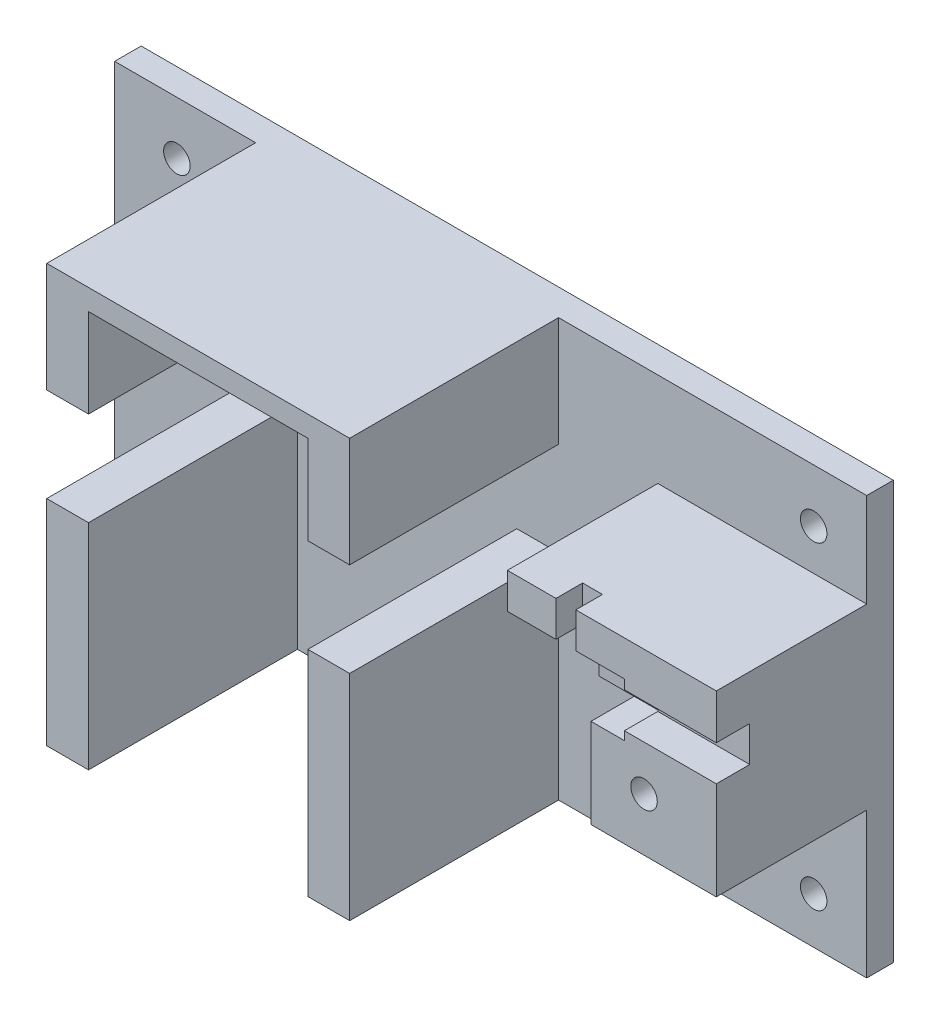
SolidWorks part; units mm, degrees
ref_plane "Front Plane" through (0, 0, 0) normal (0, 0, 1) x (1, 0, 0)
ref_plane "Top Plane" through (0, 0, 0) normal (0, 1, 0) x (1, 0, 0)
ref_plane "Right Plane" through (0, 0, 0) normal (1, 0, 0) x (0, 0, -1)
sketch "Sketch1" plane through (0, 0, 0) normal (0, 0, 1) x (1, 0, 0)
  line L1 (0, 0) -> (180, 0)
  line L2 (0, 0) -> (0, 100)
  line L3 (0, 100) -> (180, 100)
  line L4 (180, 0) -> (180, 100)
  dimension "D1" = 180
  dimension "D2" = 100
extrude "Boss-Extrude1" add sketch "Sketch1" along normal blind 6.35
sketch "Sketch2" plane through (0, 0, 6.35) normal (0, 0, 1) x (1, 0, 0)
  line L1 (96.25, 100) -> (106.25, 100)
  line L2 (96.25, 100) -> (96.25, 73.75)
  line L3 (96.25, 73.75) -> (106.25, 73.75)
  line L4 (106.25, 100) -> (106.25, 73.75)
  line L5 (180, 100) -> (0, 100) construction
  line L6 (0, 0) -> (180, 0) construction
  line L7 (70, 0) -> (70, 100)
  line L8 (96.25, 0) -> (106.25, 0)
  line L9 (96.25, 0) -> (96.25, 51.25)
  line L10 (96.25, 51.25) -> (106.25, 51.25)
  line L11 (106.25, 0) -> (106.25, 51.25)
  line L13 (96.25, 0) -> (96.25, 5)
  line L16 (0, 100) -> (0, 0) construction
  line L19 (70, 5) -> (70, 0)
  line L21 (96.25, 5) -> (96.25, 0)
  line L25 (43.75, 5) -> (43.75, 0)
  line L26 (43.75, 0) -> (43.75, 5)
  line L27 (33.75, 0) -> (33.75, 51.25)
  line L28 (43.75, 51.25) -> (33.75, 51.25)
  line L29 (43.75, 0) -> (43.75, 51.25)
  line L30 (43.75, 0) -> (33.75, 0)
  line L31 (33.75, 100) -> (33.75, 73.75)
  line L32 (43.75, 73.75) -> (33.75, 73.75)
  line L33 (43.75, 100) -> (43.75, 73.75)
  line L34 (43.75, 100) -> (33.75, 100)
  line L35 (43.75, 0) -> (43.75, 5)
  line L37 (43.75, 0) -> (96.25, 0)
  line L38 (43.75, 0) -> (43.75, 5)
  line L40 (96.25, 0) -> (96.25, 5)
  line L41 (43.75, 100) -> (96.25, 100)
  line L42 (43.75, 100) -> (43.75, 95)
  line L43 (43.75, 95) -> (96.25, 95)
  line L44 (96.25, 100) -> (96.25, 95)
  line M10 (0, 0) -> (180, 0)
  line M12 (180, 100) -> (0, 100)
  dimension "D1" = 10
  dimension "D2" = 10
  dimension "D3" = 26.25
  dimension "D4" = 70
  dimension "D5" = 22.5
  dimension "D6" = 26.25
  dimension "D8" = 5
extrude "Boss-Extrude3" add sketch "Sketch2" along normal blind 50 contours L33 L31 L32 M12 | L33 L43 L7 M12 | L7 L43 L2 M12 | L4 L2 L3 M12 | L25 L29 L28 L27 M10 | L11 L10 L9 M10 region at (101.25, 25.625, 6.35) region at (38.75, 25.625, 6.35) region at (101.25, 86.875, 6.35) region at (83.125, 97.5, 6.35) region at (56.875, 97.5, 6.35) region at (38.75, 86.875, 6.35)
sketch "Sketch3" plane through (0, 0, 6.35) normal (0, 0, 1) x (1, 0, 0)
  line L0 (180, 0) -> (180, 100) construction
  line L1 (180, 77.5) -> (150, 77.5)
  line L2 (180, 77.5) -> (180, 47.5)
  line L3 (180, 47.5) -> (150, 47.5)
  line L4 (150, 77.5) -> (150, 47.5)
  line L10 (180, 100) -> (106.25, 100) construction
  dimension "D1" = 30
  dimension "D2" = 30
  dimension "D3" = 22.5
extrude "Boss-Extrude4" add sketch "Sketch3" along normal blind 25.65
sketch "Sketch4" plane through (0, 0, 32) normal (0, 0, 1) x (1, 0, 0)
  line L0 (150, 77.5) -> (150, 47.5) construction
  line L1 (150, 69) -> (158, 69)
  line L2 (150, 69) -> (150, 56.2)
  line L3 (150, 56.2) -> (158, 56.2)
  line L4 (158, 69) -> (158, 56.2)
  line L5 (180, 77.5) -> (150, 77.5) construction
  line L6 (150, 69) -> (150, 77.5)
  line L7 (150, 77.5) -> (180, 77.5)
  line L8 (180, 77.5) -> (180, 47.5)
  line L9 (180, 47.5) -> (150, 47.5)
  line L10 (150, 47.5) -> (150, 56.2)
  line L12 (158, 58.25) -> (180, 58.25)
  line L13 (158, 58.25) -> (158, 66.75)
  line L14 (158, 66.75) -> (180, 66.75)
  line L15 (180, 58.25) -> (180, 66.75)
  line M8 (180, 47.5) -> (180, 77.5)
  line M9 (180, 77.5) -> (150, 77.5)
  line M10 (150, 77.5) -> (150, 47.5)
  line M11 (150, 47.5) -> (180, 47.5)
  dimension "D1" = 12.8
  dimension "D2" = 8.5
  dimension "D3" = 8
  dimension "D4" = 8.5
  dimension "D5" = 10.75
extrude "Boss-Extrude5" add sketch "Sketch4" along normal blind 10.35 contours L4 L14 L1 M8 M9 M10 | L12 L4 L3 M10 M11 M8 region at (165.6502, 72.3762, 32) region at (165.5893, 52.6419, 32)
sketch "Sketch5" plane through (0, 0, 32) normal (0, 0, 1) x (1, 0, 0)
  line L1 (158, 58.25) -> (180, 58.25)
  line L2 (158, 58.25) -> (158, 66.75)
  line L3 (158, 66.75) -> (180, 66.75)
  line L4 (180, 58.25) -> (180, 66.75)
extrude "Boss-Extrude6" add sketch "Sketch5" along normal blind 2.35
sketch "Sketch6" plane through (0, 0, 6.35) normal (0, 0, 1) x (1, 0, 0)
  line L0 (180, 77.5) -> (150, 77.5) construction
  line L1 (150, 69) -> (130, 69)
  line L2 (150, 69) -> (150, 77.5)
  line L3 (150, 77.5) -> (130, 77.5)
  line L4 (130, 69) -> (130, 77.5)
  dimension "D1" = 20
extrude "Boss-Extrude7" add sketch "Sketch6" along normal blind 29.625
sketch "Sketch8" plane through (0, 0, 35.975) normal (0, 0, 1) x (1, 0, 0)
  line L0 (130, 69) -> (150, 69) construction
  line L1 (150, 77.5) -> (146.375, 77.5)
  line L2 (150, 77.5) -> (150, 69)
  line L3 (150, 69) -> (146.375, 69)
  line L4 (146.375, 77.5) -> (146.375, 69)
  line L5 (130, 69) -> (150, 69) construction
  line L6 (130, 77.5) -> (141.625, 77.5)
  line L7 (130, 77.5) -> (130, 69)
  line L8 (130, 69) -> (141.625, 69)
  line L9 (141.625, 77.5) -> (141.625, 69)
  dimension "D1" = 3.625
  dimension "D2" = 4.75
extrude "Boss-Extrude8" add sketch "Sketch8" along normal up to surface (6.375 mm away) up to face at (162.6667, 71.0833, 42.35)
sketch "Sketch9" plane through (0, 0, 6.35) normal (0, 0, 1) x (1, 0, 0)
  line L0 (150, 56.2) -> (158, 56.2) construction
  line L1 (150, 69) -> (141.625, 69)
  line L2 (150, 69) -> (150, 56.2)
  line L3 (150, 56.2) -> (141.625, 56.2)
  line L4 (141.625, 69) -> (141.625, 56.2)
  line L5 (141.625, 69) -> (141.625, 77.5) construction
extrude "Boss-Extrude9" add sketch "Sketch9" along normal up to surface (25.65 mm away) up to face at (154, 62.6, 32)
sketch "Sketch10" plane through (0, 0, 6.35) normal (0, 0, 1) x (1, 0, 0)
  line L0 (33.75, 100) -> (0, 100) construction
  line L4 (180, 77.5) -> (180, 100) construction
  circle A0 centre (14.9, 87.3) radius 3.175
  circle A1 centre (167.3, 87.3) radius 3.175
  circle A2 centre (167.3, 11.1) radius 3.175
  circle A3 centre (14.9, 11.1) radius 3.175
  dimension "D1" = 6.35
  dimension "D2" = 12.7
  dimension "D3" = 12.7
  dimension "D4" = 152.4
  dimension "D5" = 152.4
  dimension "D6" = 76.2
  dimension "D7" = 76.2
extrude "Cut-Extrude1" cut sketch "Sketch10" against normal blind 6.35
sketch "Sketch11" plane through (0, 0, 6.35) normal (0, 0, 1) x (1, 0, 0)
  line L0 (180, 0) -> (180, 47.5) construction
  line L1 (150, 47.5) -> (180, 47.5)
  line L2 (150, 47.5) -> (150, 34.8)
  line L3 (150, 34.8) -> (180, 34.8)
  line L4 (180, 47.5) -> (180, 34.8)
  dimension "D1" = 12.7
extrude "Boss-Extrude10" add sketch "Sketch11" along normal up to surface (36 mm away) up to face at (162.6667, 53.9833, 42.35)
sketch "Sketch12" plane through (0, 0, 42.35) normal (0, 0, 1) x (1, 0, 0)
  line L0 (180, 77.5) -> (146.375, 77.5) construction
  line L1 (180, 34.8) -> (150, 34.8)
  line L2 (180, 34.8) -> (180, 77.5)
  line L3 (180, 77.5) -> (150, 77.5)
  line L4 (150, 34.8) -> (150, 77.5)
  line L10 (146.375, 69) -> (158, 69) construction
  line L11 (130, 77.5) -> (150, 77.5)
  line L12 (130, 77.5) -> (130, 69)
  line L13 (130, 69) -> (150, 69)
  line L14 (150, 77.5) -> (150, 69)
  circle A0 centre (162.7, 47.5) radius 3.175
  dimension "D1" = 6.35
  dimension "D2" = 12.7
  dimension "D3" = 12.7
extrude "Cut-Extrude2" cut sketch "Sketch12" against normal blind 10 contours A0 region at (162.7, 47.5, 42.35)
